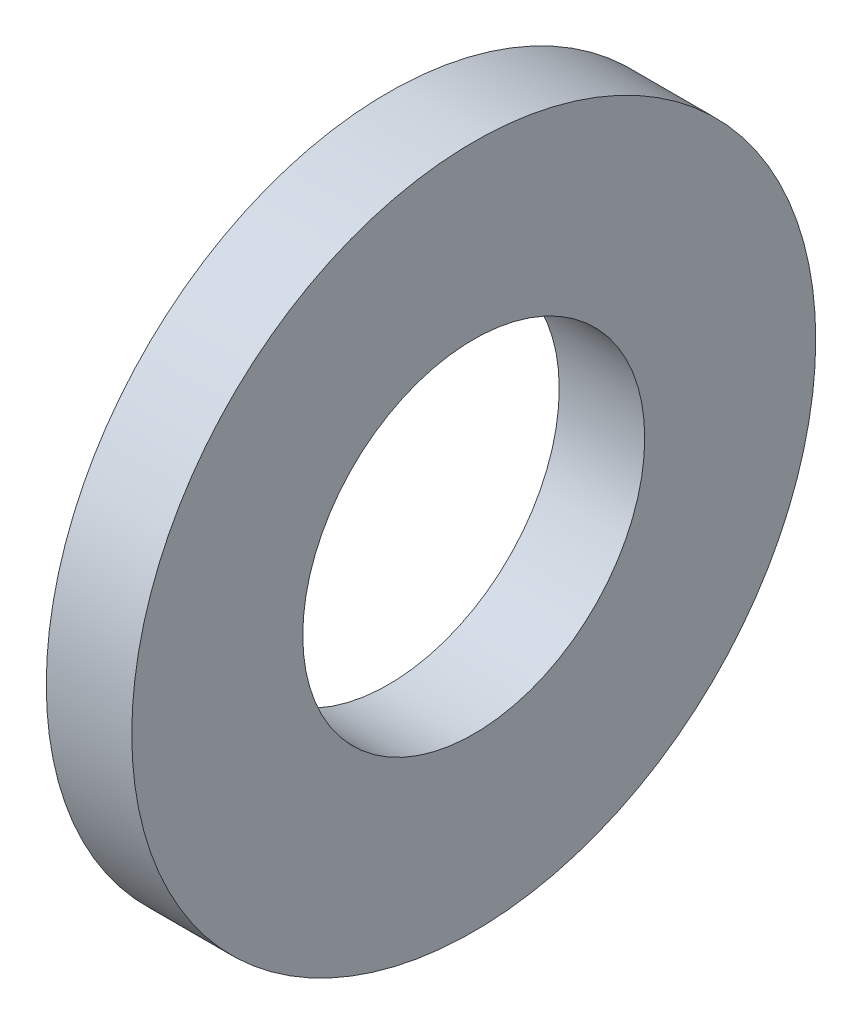
SolidWorks part; units mm, degrees
material "Acier allié"
ref_plane "Plan1" through (0, 0, 0) normal (0, 0, 1) x (1, 0, 0)
ref_plane "Plan2" through (0, 0, 0) normal (0, 1, 0) x (1, 0, 0)
ref_plane "Plan3" through (0, 0, 0) normal (1, 0, 0) x (0, 0, -1)
sketch "Esquisse1" plane through (0, 0, 0) normal (0, 1, 0) x (1, 0, 0)
  line L0 (0, 0) -> (40, 0) construction
  line L2 (0, 4) -> (1, 4)
  line L3 (0, 4) -> (0, 2)
  line L4 (0, 2) -> (1, 2)
  line L5 (1, 4) -> (1, 2)
  dimension "D1" = 2
  dimension "D2" = 4
  dimension "D3" = 1
revolve "Base-Révolution" add sketch "Esquisse1" angle 360 about L0
ref_axis "Axe1" through (-50, 0, 0) along (1, 0, 0)
